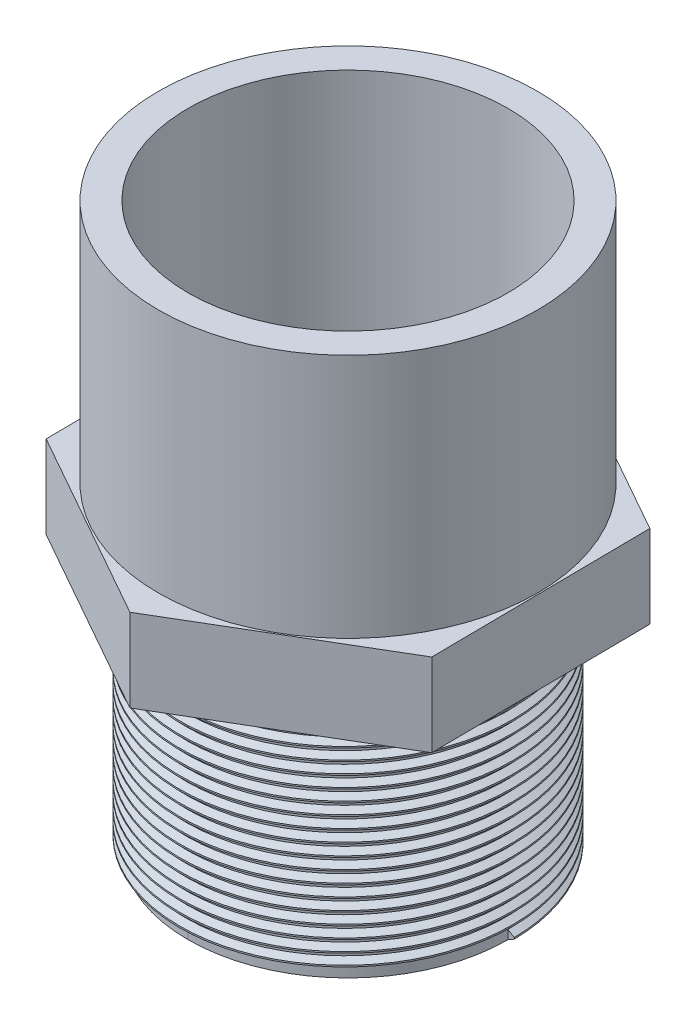
SolidWorks part; units mm, degrees
ref_plane "Front Plane" through (0, 0, 0) normal (0, 0, 1) x (1, 0, 0)
ref_plane "Top Plane" through (0, 0, 0) normal (0, 1, 0) x (1, 0, 0)
ref_plane "Right Plane" through (0, 0, 0) normal (1, 0, 0) x (0, 0, -1)
sketch "Sketch1" plane through (0, 0, 0) normal (0, 1, 0) x (1, 0, 0)
  line L1 (16.2101, -9.1362) -> (16.0172, 9.4703)
  line L2 (16.0172, 9.4703) -> (-0.1929, 18.6064)
  line L3 (-0.1929, 18.6064) -> (-16.2101, 9.1362)
  line L4 (-16.2101, 9.1362) -> (-16.0172, -9.4703)
  line L5 (-16.0172, -9.4703) -> (0.1929, -18.6064)
  line L6 (0.1929, -18.6064) -> (16.2101, -9.1362)
  circle A0 centre (0, 0) radius 16
  circle A1 centre (0, 0) radius 13.5
  circle A2 centre (0, 0) radius 16.1145 construction
  circle A3 centre (0, 0) radius 9.55
  circle A4 centre (0, 0) radius 11.5
  dimension "D1" = 32
  dimension "D2" = 27
  dimension "D3" = 19.1
  dimension "D4" = 23
extrude "Boss-Extrude3" add sketch "Sketch1" along normal blind 20.7 and the other way blind 7 contours A0 A1 region at (-15.5475, 0, 0)
extrude "Boss-Extrude4" add sketch "Sketch1<5>" against normal blind 7 separate body contours L5 L6 L1 L2 L3 L4 A0 region at (8.1764, 0, 13.8288)
sketch "Sketch1<5>" plane through (0, 0, 0) normal (0, 1, 0) x (1, 0, 0) same geometry as "Sketch1"
extrude "Boss-Extrude5" add sketch "Sketch1<6>" against normal blind 26.6 separate body contours A1 A3 region at (-13.1182, 0, 0)
sketch "Sketch1<6>" plane through (0, 0, 0) normal (0, 1, 0) x (1, 0, 0) same geometry as "Sketch1"
thread "Thread1" pitch 1 method extrude profile "Thread Profile2" start angle 0, offset 0, length 19, pitch 1, diameter 27
ref_plane "Plane2" through (13.5, -26.6, 0) normal (0, 0, 1) x (1, 0, 0)
sketch "Thread Profile2" plane through (13.5, -26.6, 0) normal (0, 0, 1) x (1, 0, 0)
  line L0 (0, 0) -> (0, 1) construction
  line L1 (0, 0) -> (0.5413, 0.3125)
  line L2 (0.5413, 0.3125) -> (0.5413, 0.4375)
  line L3 (0.5413, 0.4375) -> (0, 0.75)
  line L4 (0.5413, 0.375) -> (0, 0.375) construction
  line L11 (0, 0) -> (0, 0.75)
  point P2 (0, 0)
  dimension "Pitch" = 1
  dimension "Profile_Angle" = 60
  dimension "Profile_Land" = 0.125
  dimension "Profile_Height" = 0.5413
